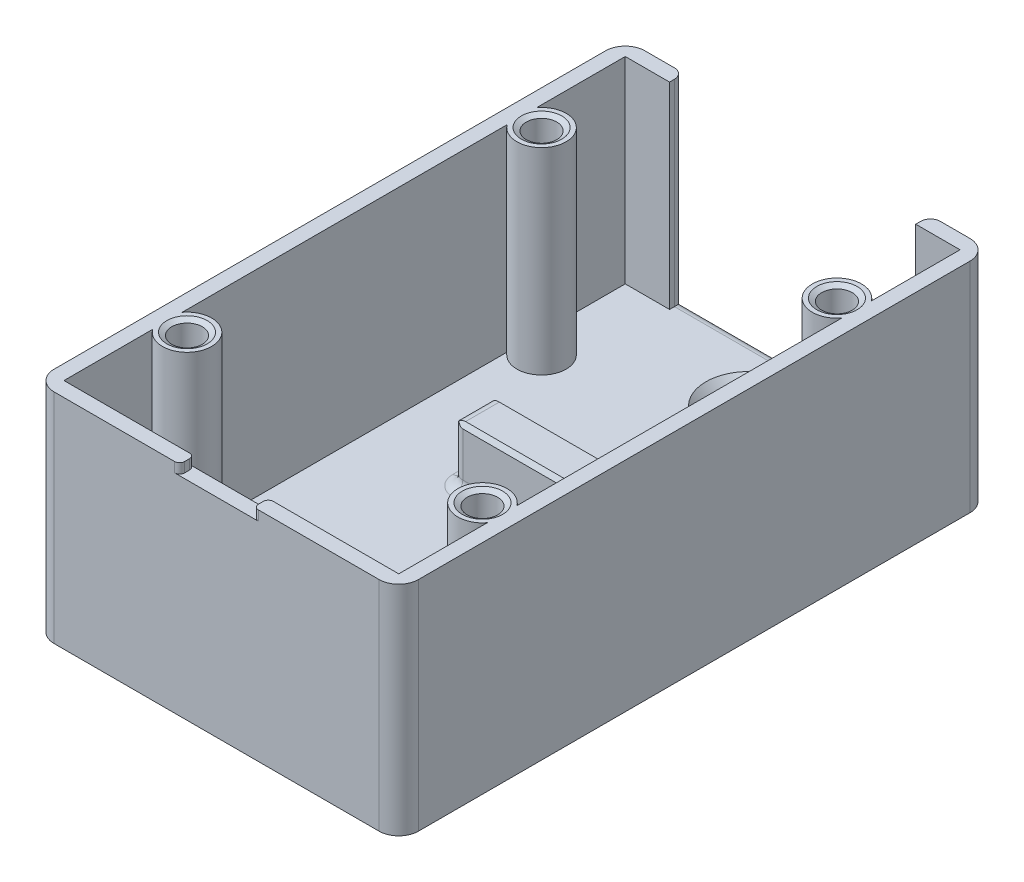
SolidWorks part; units mm, degrees
ref_plane "Спереди" through (0, 0, 0) normal (0, 0, 1) x (1, 0, 0)
ref_plane "Сверху" through (0, 0, 0) normal (0, 1, 0) x (1, 0, 0)
ref_plane "Справа" through (0, 0, 0) normal (1, 0, 0) x (0, 0, -1)
sketch "Эскиз1" plane through (0, 0, 0) normal (0, 1, 0) x (1, 0, 0)
  line L1 (-18.5, -30) -> (18.5, -30)
  line L2 (-18.5, -30) -> (-18.5, 30)
  line L3 (-18.5, 30) -> (18.5, 30)
  line L4 (18.5, -30) -> (18.5, 30)
  line L5 (0, 30) -> (0, -30) construction
  line L6 (-18.5, 0) -> (18.5, 0) construction
  circle A0 centre (0, 24) radius 2.3
  circle A1 centre (0, -24) radius 2.3
  point P0 (0, 0)
  dimension "D1" = 48
  dimension "D2" = 4.6
  dimension "D4" = 6
  dimension "D3" = 60
  dimension "D5" = 37
extrude "Бобышка-Вытянуть1" add sketch "Эскиз1" along normal blind 3
chamfer "Фаска1" distance 2 angle 45 2 edges at (0, 3, 26.3) (0, 3, -21.7)
sketch "Эскиз2" plane through (0, 3, 0) normal (0, 1, 0) x (1, 0, 0)
  line L0 (-18.5, 30) -> (18.5, 30)
  line L2 (-18.5, 30) -> (-18.5, -30)
  line L3 (-18.5, -30) -> (18.5, -30)
  line L4 (18.5, 30) -> (18.5, -30)
extrude "Вытянуть-Тонкостенный1" add sketch "Эскиз2" along normal blind 20 thin
sketch "Эскиз3" plane through (0, 23, 0) normal (0, 1, 0) x (1, 0, 0)
  line L0 (0, 32.0771) -> (0, 0) construction
  line L2 (-12.5, 27.9629) -> (12.5, 27.9629)
  line L3 (-12.5, 27.9629) -> (-12.5, 30.9933)
  line L4 (-12.5, 30.9933) -> (12.5, 30.9933)
  line L5 (12.5, 27.9629) -> (12.5, 30.9933)
  line L6 (0, 30.9933) -> (0, 27.9629) construction
  line L7 (-12.5, 29.4781) -> (12.5, 29.4781) construction
  point P3 (0, 29.4781)
  dimension "D1" = 25
extrude "Вырез-Вытянуть1" cut sketch "Эскиз3" against normal up to surface (20 mm away) up to face at (0, 3, 0)
sketch "Эскиз4" plane through (0, 3, 0) normal (0, 1, 0) x (1, 0, 0)
  line L0 (0, 32.478) -> (0, 0) construction
  line L1 (0, 0) -> (39.8357, 0) construction
  line L3 (18.5, -30) -> (18.5, 30) construction
  circle A0 centre (15, 18) radius 2.5
  circle A1 centre (-15, 18) radius 2.5
  circle A2 centre (15, -18) radius 2.5
  circle A3 centre (-15, -18) radius 2.5
  dimension "D1" = 5
  dimension "D3" = 3.5
  dimension "D2" = 18
extrude "Бобышка-Вытянуть2" add sketch "Эскиз4" along normal up to surface (20 mm away) up to face at (0, 23, -9.75)
sketch "Эскиз5" plane through (0, 23, 0) normal (0, 1, 0) x (1, 0, 0)
  line L0 (18.5, -30) -> (18.5, 30) construction
  circle A0 centre (15, 18) radius 1.55
  circle A1 centre (15, -18) radius 1.55
  circle A2 centre (-15, -18) radius 1.55
  circle A3 centre (-15, 18) radius 1.55
  dimension "D1" = 3.1
  dimension "D2" = 3.5
extrude "Вырез-Вытянуть2" cut sketch "Эскиз5" against normal blind 10
sketch "Эскиз6" plane through (0, 3, 0) normal (0, 1, 0) x (1, 0, 0)
  line L1 (-8, 6) -> (8, 6)
  line L2 (-8, 6) -> (-8, 2)
  line L3 (-8, 2) -> (8, 2)
  line L4 (8, 6) -> (8, 2)
  line L7 (0, 0) -> (0, 12.6053) construction
  line L8 (17, 28.5) -> (12.5, 28.5) construction
  point P6 (0, 6)
  dimension "D1" = 4
  dimension "D2" = 26.5
  dimension "D3" = 16
extrude "Бобышка-Вытянуть3" add sketch "Эскиз6" along normal blind 6
sketch "Эскиз7" plane through (0, 23, 0) normal (0, 1, 0) x (1, 0, 0)
  line L1 (-3.75, -30.9828) -> (3.75, -30.9828)
  line L2 (-3.75, -30.9828) -> (-3.75, -26.3156)
  line L3 (-3.75, -26.3156) -> (3.75, -26.3156)
  line L4 (3.75, -30.9828) -> (3.75, -26.3156)
  line L5 (0, -26.3156) -> (0, -30.9828) construction
  line L6 (-3.75, -28.6492) -> (3.75, -28.6492) construction
  point P0 (0, -28.6492)
  dimension "D1" = 7.5
extrude "Вырез-Вытянуть3" cut sketch "Эскиз7" against normal blind 1
fillet "Скругление2" radius 0.5 4 edges at (-3.75, 22.5, 28.5) (-3.75, 22.5, 30) (3.75, 22.5, 30) (3.75, 22.5, 28.5)
fillet "Скругление3" radius 2 4 edges at (18.5, 11.5, -30) (-18.5, 11.5, -30) (-18.5, 11.5, 30) (18.5, 11.5, 30)
chamfer "Фаска4" distance 1.5 angle 30 10 edges at (0, 0, 26.3) (0, 0, -30) (-18.5, 0, 0) (0, 0, 30) (18.5, 0, 0) (0, 0, -21.7) (-17.9142, 0, -29.4142) (-17.9142, 0, 29.4142) (17.9142, 0, 29.4142) (17.9142, 0, -29.4142)
fillet "Скругление4" radius 1 10 edges at (0, 3, -6) (0, 3, -2) (8, 3, -4) (8, 6, -2) (8, 6, -6) (-8, 3, -4) (-8, 6, -6) (-8, 6, -2) (8, 9, -4) (-8, 9, -4)
chamfer "Фаска5" distance 0.5 angle 30 2 edges at (0, 9, -6) (0, 9, -2)
chamfer "Фаска6" distance 0.5 angle 30 4 edges at (-15, 23, 19.55) (15, 23, 19.55) (15, 23, -16.45) (-15, 23, -16.45)
fillet "Скругление5" radius 1 3 edges at (12.5, 13, -30) (-12.5, 13, -30) (0, 3, -30)
